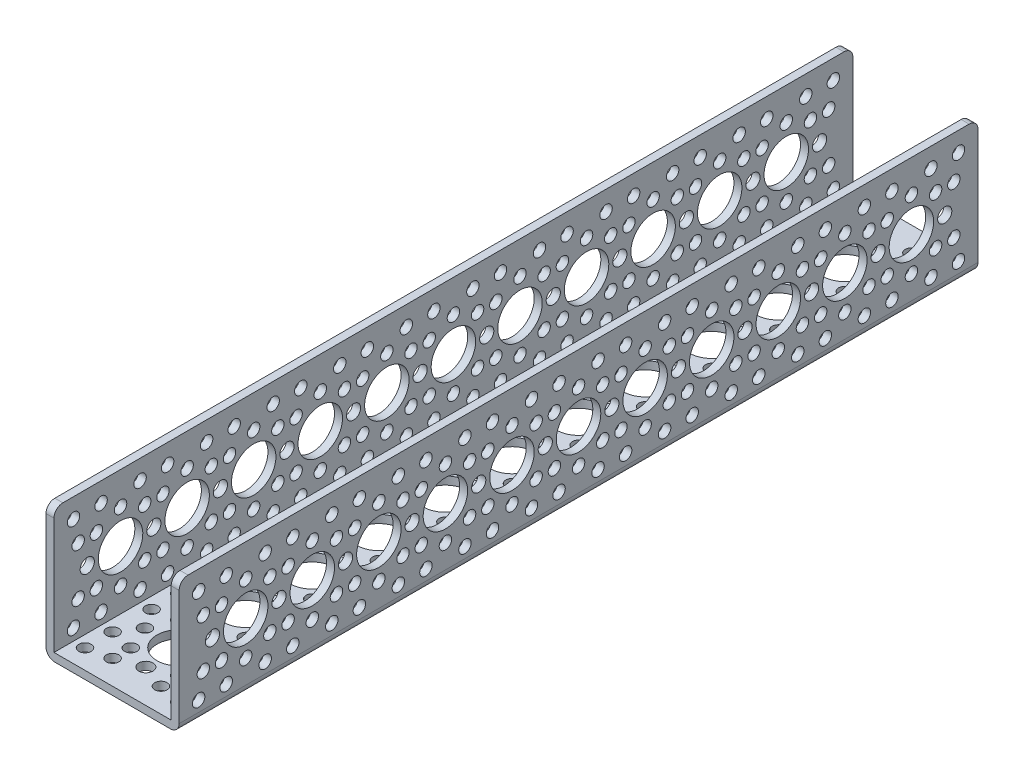
SolidWorks part; units mm, degrees
ref_plane "Front Plane" through (0, 0, 0) normal (0, 0, 1) x (1, 0, 0)
ref_plane "Top Plane" through (0, 0, 0) normal (0, 1, 0) x (1, 0, 0)
ref_plane "Right Plane" through (0, 0, 0) normal (1, 0, 0) x (0, 0, -1)
ref_plane "Plane1" through (38.1, 0, 0) normal (1, 0, 0) x (0, 0, -1)
sketch "Sketch1" plane through (38.1, 0, 0) normal (1, 0, 0) x (0, 0, -1)
  line L0 (0, 38.1) -> (-228.6, 38.1)
  line L1 (-228.6, 38.1) -> (-228.6, 0)
  line L2 (-228.6, 0) -> (0, 0)
  line L3 (0, 0) -> (0, 38.1)
extrude "Boss-Extrude1" add sketch "Sketch1" against normal blind 38.1
sketch "Sketch2" plane through (0, 0, 228.6) normal (0, 0, 1) x (1, 0, 0)
  line L0 (35.814, 38.1) -> (2.286, 38.1)
  line L1 (2.286, 38.1) -> (2.286, 2.286)
  line L2 (2.286, 2.286) -> (35.814, 2.286)
  line L3 (35.814, 2.286) -> (35.814, 38.1)
extrude "Cut-Extrude1" cut sketch "Sketch2" against normal through all
hole_wizard "Hole1" positions "Sketch4" profile "Sketch3" legacy
sketch "Sketch4" plane through (0, 0, 0) normal (-1, 0, 0) x (0, 0, 1)
  point P0 (38.1, 19.05)
  point P1 (19.05, 19.05)
  point P2 (57.15, 19.05)
  point P3 (76.2, 19.05)
  point P4 (95.25, 19.05)
  point P5 (114.3, 19.05)
  point P6 (133.35, 19.05)
  point P7 (152.4, 19.05)
  point P8 (171.45, 19.05)
  point P9 (190.5, 19.05)
  point P10 (209.55, 19.05)
sketch "Sketch3" plane through (0, 19.05, 38.1) normal (0, 1, 0) x (0, 0, 1)
  line L0 (0, 0) -> (0, 2.286)
  line L1 (0, 2.286) -> (6.3627, 2.286)
  line L2 (6.3627, 2.286) -> (6.3627, 0)
  line L3 (6.3627, 0) -> (0, 0)
  line L4 (0, 110) -> (0, -10) construction
  dimension "Diameter" = 12.7254
  dimension "Depth" = 2.286
hole_wizard "#5 Clearance Hole1" positions "Sketch6" profile "Sketch5" hole size "#5" standard "ANSI Inch"
sketch "Sketch6" plane through (0, 0, 0) normal (-1, 0, 0) x (0, 0, 1)
  point P0 (215.1296, 5.5796)
  point P1 (221.6852, 12.1352)
  point P2 (215.1296, 32.5204)
  point P3 (221.6852, 25.9648)
  point P4 (13.4704, 5.5796)
  point P5 (6.9148, 12.1352)
  point P6 (13.4704, 32.5204)
  point P7 (6.9148, 25.9648)
  point P8 (196.0796, 5.5796)
  point P9 (177.0296, 5.5796)
  point P10 (157.9796, 5.5796)
  point P11 (138.9296, 5.5796)
  point P12 (119.8796, 5.5796)
  point P13 (100.8296, 5.5796)
  point P14 (81.7796, 5.5796)
  point P15 (62.7296, 5.5796)
  point P16 (43.6796, 5.5796)
  point P17 (24.6296, 5.5796)
  point P18 (196.0796, 32.5204)
  point P19 (177.0296, 32.5204)
  point P20 (157.9796, 32.5204)
  point P21 (138.9296, 32.5204)
  point P22 (119.8796, 32.5204)
  point P23 (100.8296, 32.5204)
  point P24 (81.7796, 32.5204)
  point P25 (62.7296, 32.5204)
  point P26 (43.6796, 32.5204)
  point P27 (24.6296, 32.5204)
  point P28 (223.0204, 5.5796)
  point P29 (223.0204, 32.5204)
  point P30 (203.9704, 5.5796)
  point P31 (203.9704, 32.5204)
  point P32 (184.9204, 5.5796)
  point P33 (184.9204, 32.5204)
  point P34 (165.8704, 5.5796)
  point P35 (165.8704, 32.5204)
  point P36 (146.8204, 5.5796)
  point P37 (146.8204, 32.5204)
  point P38 (127.7704, 5.5796)
  point P39 (127.7704, 32.5204)
  point P40 (108.7204, 5.5796)
  point P41 (108.7204, 32.5204)
  point P42 (89.6704, 5.5796)
  point P43 (89.6704, 32.5204)
  point P44 (70.6204, 5.5796)
  point P45 (70.6204, 32.5204)
  point P46 (51.5704, 5.5796)
  point P47 (51.5704, 32.5204)
  point P48 (202.6352, 12.1352)
  point P49 (209.55, 9.271)
  point P50 (216.4648, 12.1352)
  point P51 (216.4648, 25.9648)
  point P52 (209.55, 28.829)
  point P53 (183.5852, 12.1352)
  point P54 (190.5, 9.271)
  point P55 (197.4148, 12.1352)
  point P56 (197.4148, 25.9648)
  point P57 (190.5, 28.829)
  point P58 (164.5352, 12.1352)
  point P59 (171.45, 9.271)
  point P60 (178.3648, 12.1352)
  point P61 (178.3648, 25.9648)
  point P62 (171.45, 28.829)
  point P63 (145.4852, 12.1352)
  point P64 (152.4, 9.271)
  point P65 (159.3148, 12.1352)
  point P66 (159.3148, 25.9648)
  point P67 (152.4, 28.829)
  point P68 (126.4352, 12.1352)
  point P69 (133.35, 9.271)
  point P70 (140.2648, 12.1352)
  point P71 (140.2648, 25.9648)
  point P72 (133.35, 28.829)
  point P73 (107.3852, 12.1352)
  point P74 (114.3, 9.271)
  point P75 (121.2148, 12.1352)
  point P76 (121.2148, 25.9648)
  point P77 (114.3, 28.829)
  point P78 (88.3352, 12.1352)
  point P79 (95.25, 9.271)
  point P80 (102.1648, 12.1352)
  point P81 (102.1648, 25.9648)
  point P82 (95.25, 28.829)
  point P83 (69.2852, 12.1352)
  point P84 (76.2, 9.271)
  point P85 (83.1148, 12.1352)
  point P86 (83.1148, 25.9648)
  point P87 (76.2, 28.829)
  point P88 (50.2352, 12.1352)
  point P89 (57.15, 9.271)
  point P90 (64.0648, 12.1352)
  point P91 (64.0648, 25.9648)
  point P92 (57.15, 28.829)
  point P93 (31.1852, 12.1352)
  point P94 (38.1, 9.271)
  point P95 (45.0148, 12.1352)
  point P96 (45.0148, 25.9648)
  point P97 (38.1, 28.829)
  point P98 (202.6352, 25.9648)
  point P99 (183.5852, 25.9648)
  point P100 (164.5352, 25.9648)
  point P101 (145.4852, 25.9648)
  point P102 (126.4352, 25.9648)
  point P103 (107.3852, 25.9648)
  point P104 (88.3352, 25.9648)
  point P105 (69.2852, 25.9648)
  point P106 (50.2352, 25.9648)
  point P107 (31.1852, 25.9648)
  point P108 (32.5204, 5.5796)
  point P109 (32.5204, 32.5204)
  point P110 (5.5796, 5.5796)
  point P111 (5.5796, 32.5204)
  point P112 (12.1352, 12.1352)
  point P113 (19.05, 9.271)
  point P114 (25.9648, 12.1352)
  point P115 (25.9648, 25.9648)
  point P116 (19.05, 28.829)
  point P117 (12.1352, 25.9648)
sketch "Sketch5" plane through (0, 5.5796, 215.1296) normal (0, 1, 0) x (0, 0, 1)
  line L0 (0, 0) -> (0, 2.286)
  line L1 (0, 2.286) -> (1.778, 2.286)
  line L2 (1.778, 2.286) -> (1.778, 0)
  line L5 (1.778, 0) -> (0, 0)
  line L11 (0, -6.35) -> (0, 107.95) construction
  dimension "Thru Hole Dia." = 3.556
  dimension "Thru Hole Depth" = 2.286
hole_wizard "#6 Clearance Hole1" positions "Sketch8" profile "Sketch7" hole size "#6" standard "ANSI Inch"
sketch "Sketch8" plane through (0, 0, 0) normal (-1, 0, 0) x (0, 0, 1)
  point P0 (219.075, 19.05)
  point P1 (200.025, 19.05)
  point P2 (180.975, 19.05)
  point P3 (161.925, 19.05)
  point P4 (142.875, 19.05)
  point P5 (123.825, 19.05)
  point P6 (104.775, 19.05)
  point P7 (85.725, 19.05)
  point P8 (66.675, 19.05)
  point P9 (47.625, 19.05)
  point P10 (28.575, 19.05)
  point P11 (9.525, 19.05)
sketch "Sketch7" plane through (0, 19.05, 219.075) normal (0, 1, 0) x (0, 0, 1)
  line L0 (0, 0) -> (0, 2.286)
  line L1 (0, 2.286) -> (2.032, 2.286)
  line L2 (2.032, 2.286) -> (2.032, 0)
  line L5 (2.032, 0) -> (0, 0)
  line L11 (0, -6.35) -> (0, 107.95) construction
  dimension "Thru Hole Dia." = 4.064
  dimension "Thru Hole Depth" = 2.286
hole_wizard "Hole2" positions "Sketch10" profile "Sketch9" legacy
sketch "Sketch10" plane through (0, 0, 0) normal (0, -1, 0) x (-1, 0, 0)
  point P0 (-19.05, -209.55)
  point P1 (-19.05, -190.5)
  point P2 (-19.05, -171.45)
  point P3 (-19.05, -152.4)
  point P4 (-19.05, -133.35)
  point P5 (-19.05, -114.3)
  point P6 (-19.05, -95.25)
  point P7 (-19.05, -76.2)
  point P8 (-19.05, -57.15)
  point P9 (-19.05, -38.1)
  point P10 (-19.05, -19.05)
sketch "Sketch9" plane through (19.05, 0, 209.55) normal (1, 0, 0) x (0, 0, -1)
  line L0 (0, 0) -> (0, 38.1)
  line L1 (0, 38.1) -> (6.3627, 38.1)
  line L2 (6.3627, 38.1) -> (6.3627, 0)
  line L3 (6.3627, 0) -> (0, 0)
  line L4 (0, 110) -> (0, -10) construction
  dimension "Diameter" = 12.7254
  dimension "Depth" = 38.1
hole_wizard "#6 Clearance Hole2" positions "Sketch12" profile "Sketch11" hole size "#6" standard "ANSI Inch"
sketch "Sketch12" plane through (0, 0, 0) normal (0, -1, 0) x (-1, 0, 0)
  point P0 (-19.05, -219.075)
  point P1 (-19.05, -200.025)
  point P2 (-19.05, -180.975)
  point P3 (-19.05, -161.925)
  point P4 (-19.05, -142.875)
  point P5 (-19.05, -123.825)
  point P6 (-19.05, -104.775)
  point P7 (-19.05, -85.725)
  point P8 (-19.05, -66.675)
  point P9 (-19.05, -47.625)
  point P10 (-19.05, -28.575)
  point P11 (-19.05, -9.525)
sketch "Sketch11" plane through (19.05, 0, 219.075) normal (1, 0, 0) x (0, 0, -1)
  line L0 (0, 0) -> (0, 38.1)
  line L1 (0, 38.1) -> (2.032, 38.1)
  line L2 (2.032, 38.1) -> (2.032, 0)
  line L5 (2.032, 0) -> (0, 0)
  line L11 (0, -6.35) -> (0, 107.95) construction
  dimension "Thru Hole Dia." = 4.064
  dimension "Thru Hole Depth" = 38.1
hole_wizard "#5 Clearance Hole2" positions "Sketch14" profile "Sketch13" hole size "#5" standard "ANSI Inch"
sketch "Sketch14" plane through (0, 0, 0) normal (0, -1, 0) x (-1, 0, 0)
  point P0 (-5.5796, -223.0204)
  point P1 (-5.5796, -215.1296)
  point P2 (-12.1352, -221.6852)
  point P3 (-32.5204, -223.0204)
  point P4 (-32.5204, -215.1296)
  point P5 (-25.9648, -221.6852)
  point P6 (-5.5796, -203.9704)
  point P7 (-5.5796, -196.0796)
  point P8 (-32.5204, -203.9704)
  point P9 (-32.5204, -196.0796)
  point P10 (-5.5796, -184.9204)
  point P11 (-5.5796, -177.0296)
  point P12 (-32.5204, -184.9204)
  point P13 (-32.5204, -177.0296)
  point P14 (-5.5796, -165.8704)
  point P15 (-5.5796, -157.9796)
  point P16 (-32.5204, -165.8704)
  point P17 (-32.5204, -157.9796)
  point P18 (-5.5796, -146.8204)
  point P19 (-5.5796, -138.9296)
  point P20 (-32.5204, -146.8204)
  point P21 (-32.5204, -138.9296)
  point P22 (-5.5796, -127.7704)
  point P23 (-5.5796, -119.8796)
  point P24 (-32.5204, -127.7704)
  point P25 (-32.5204, -119.8796)
  point P26 (-5.5796, -108.7204)
  point P27 (-5.5796, -100.8296)
  point P28 (-32.5204, -108.7204)
  point P29 (-32.5204, -100.8296)
  point P30 (-5.5796, -89.6704)
  point P31 (-5.5796, -81.7796)
  point P32 (-32.5204, -89.6704)
  point P33 (-32.5204, -81.7796)
  point P34 (-5.5796, -70.6204)
  point P35 (-5.5796, -62.7296)
  point P36 (-32.5204, -70.6204)
  point P37 (-32.5204, -62.7296)
  point P38 (-5.5796, -51.5704)
  point P39 (-5.5796, -43.6796)
  point P40 (-32.5204, -51.5704)
  point P41 (-32.5204, -43.6796)
  point P42 (-12.1352, -202.6352)
  point P43 (-9.271, -209.55)
  point P44 (-12.1352, -216.4648)
  point P45 (-25.9648, -216.4648)
  point P46 (-28.829, -209.55)
  point P47 (-25.9648, -202.6352)
  point P48 (-12.1352, -183.5852)
  point P49 (-9.271, -190.5)
  point P50 (-12.1352, -197.4148)
  point P51 (-25.9648, -197.4148)
  point P52 (-28.829, -190.5)
  point P53 (-25.9648, -183.5852)
  point P54 (-12.1352, -164.5352)
  point P55 (-9.271, -171.45)
  point P56 (-12.1352, -178.3648)
  point P57 (-25.9648, -178.3648)
  point P58 (-28.829, -171.45)
  point P59 (-25.9648, -164.5352)
  point P60 (-12.1352, -145.4852)
  point P61 (-9.271, -152.4)
  point P62 (-12.1352, -159.3148)
  point P63 (-25.9648, -159.3148)
  point P64 (-28.829, -152.4)
  point P65 (-25.9648, -145.4852)
  point P66 (-12.1352, -126.4352)
  point P67 (-9.271, -133.35)
  point P68 (-12.1352, -140.2648)
  point P69 (-25.9648, -140.2648)
  point P70 (-28.829, -133.35)
  point P71 (-25.9648, -126.4352)
  point P72 (-12.1352, -107.3852)
  point P73 (-9.271, -114.3)
  point P74 (-12.1352, -121.2148)
  point P75 (-25.9648, -121.2148)
  point P76 (-28.829, -114.3)
  point P77 (-25.9648, -107.3852)
  point P78 (-12.1352, -88.3352)
  point P79 (-9.271, -95.25)
  point P80 (-12.1352, -102.1648)
  point P81 (-25.9648, -102.1648)
  point P82 (-28.829, -95.25)
  point P83 (-25.9648, -88.3352)
  point P84 (-12.1352, -69.2852)
  point P85 (-9.271, -76.2)
  point P86 (-12.1352, -83.1148)
  point P87 (-25.9648, -83.1148)
  point P88 (-28.829, -76.2)
  point P89 (-25.9648, -69.2852)
  point P90 (-12.1352, -50.2352)
  point P91 (-9.271, -57.15)
  point P92 (-12.1352, -64.0648)
  point P93 (-25.9648, -64.0648)
  point P94 (-28.829, -57.15)
  point P95 (-25.9648, -50.2352)
  point P96 (-9.271, -38.1)
  point P97 (-12.1352, -45.0148)
  point P98 (-25.9648, -45.0148)
  point P99 (-28.829, -38.1)
  point P100 (-5.5796, -32.5204)
  point P101 (-5.5796, -24.6296)
  point P102 (-12.1352, -31.1852)
  point P103 (-32.5204, -32.5204)
  point P104 (-32.5204, -24.6296)
  point P105 (-25.9648, -31.1852)
  point P106 (-5.5796, -5.5796)
  point P107 (-5.5796, -13.4704)
  point P108 (-12.1352, -6.9148)
  point P109 (-32.5204, -5.5796)
  point P110 (-32.5204, -13.4704)
  point P111 (-25.9648, -6.9148)
  point P112 (-12.1352, -12.1352)
  point P113 (-9.271, -19.05)
  point P114 (-12.1352, -25.9648)
  point P115 (-25.9648, -25.9648)
  point P116 (-28.829, -19.05)
  point P117 (-25.9648, -12.1352)
sketch "Sketch13" plane through (5.5796, 0, 223.0204) normal (1, 0, 0) x (0, 0, -1)
  line L0 (0, 0) -> (0, 38.1)
  line L1 (0, 38.1) -> (1.778, 38.1)
  line L2 (1.778, 38.1) -> (1.778, 0)
  line L5 (1.778, 0) -> (0, 0)
  line L11 (0, -6.35) -> (0, 107.95) construction
  dimension "Thru Hole Dia." = 3.556
  dimension "Thru Hole Depth" = 38.1
hole_wizard "Hole3" positions "Sketch16" profile "Sketch15" legacy
sketch "Sketch16" plane through (38.1, 0, 0) normal (1, 0, 0) x (0, 0, -1)
  point P0 (-38.1, 19.05)
  point P1 (-19.05, 19.05)
  point P2 (-57.15, 19.05)
  point P3 (-76.2, 19.05)
  point P4 (-95.25, 19.05)
  point P5 (-114.3, 19.05)
  point P6 (-133.35, 19.05)
  point P7 (-152.4, 19.05)
  point P8 (-171.45, 19.05)
  point P9 (-190.5, 19.05)
  point P10 (-209.55, 19.05)
sketch "Sketch15" plane through (38.1, 19.05, 38.1) normal (0, 1, 0) x (0, 0, -1)
  line L0 (0, 0) -> (0, 38.1)
  line L1 (0, 38.1) -> (6.3627, 38.1)
  line L2 (6.3627, 38.1) -> (6.3627, 0)
  line L3 (6.3627, 0) -> (0, 0)
  line L4 (0, 110) -> (0, -10) construction
  dimension "Diameter" = 12.7254
  dimension "Depth" = 38.1
hole_wizard "#6 Clearance Hole3" positions "Sketch18" profile "Sketch17" hole size "#6" standard "ANSI Inch"
sketch "Sketch18" plane through (38.1, 0, 0) normal (1, 0, 0) x (0, 0, -1)
  point P0 (-200.025, 19.05)
  point P1 (-161.925, 19.05)
  point P2 (-123.825, 19.05)
  point P3 (-85.725, 19.05)
  point P4 (-47.625, 19.05)
  point P5 (-9.525, 19.05)
  point P6 (-28.575, 19.05)
  point P7 (-66.675, 19.05)
  point P8 (-104.775, 19.05)
  point P9 (-142.875, 19.05)
  point P10 (-180.975, 19.05)
  point P11 (-219.075, 19.05)
sketch "Sketch17" plane through (38.1, 19.05, 200.025) normal (0, 1, 0) x (0, 0, -1)
  line L0 (0, 0) -> (0, 38.1)
  line L1 (0, 38.1) -> (2.032, 38.1)
  line L2 (2.032, 38.1) -> (2.032, 0)
  line L5 (2.032, 0) -> (0, 0)
  line L11 (0, -6.35) -> (0, 107.95) construction
  dimension "Thru Hole Dia." = 4.064
  dimension "Thru Hole Depth" = 38.1
hole_wizard "#5 Clearance Hole3" positions "Sketch20" profile "Sketch19" hole size "#5" standard "ANSI Inch"
sketch "Sketch20" plane through (38.1, 0, 0) normal (1, 0, 0) x (0, 0, -1)
  point P0 (-215.1296, 5.5796)
  point P1 (-215.1296, 32.5204)
  point P2 (-13.4704, 5.5796)
  point P3 (-196.0796, 5.5796)
  point P4 (-157.9796, 5.5796)
  point P5 (-119.8796, 5.5796)
  point P6 (-81.7796, 5.5796)
  point P7 (-43.6796, 5.5796)
  point P8 (-196.0796, 32.5204)
  point P9 (-157.9796, 32.5204)
  point P10 (-119.8796, 32.5204)
  point P11 (-81.7796, 32.5204)
  point P12 (-43.6796, 32.5204)
  point P13 (-223.0204, 5.5796)
  point P14 (-203.9704, 5.5796)
  point P15 (-184.9204, 5.5796)
  point P16 (-165.8704, 5.5796)
  point P17 (-146.8204, 5.5796)
  point P18 (-127.7704, 5.5796)
  point P19 (-108.7204, 5.5796)
  point P20 (-89.6704, 5.5796)
  point P21 (-70.6204, 5.5796)
  point P22 (-51.5704, 5.5796)
  point P23 (-209.55, 9.271)
  point P24 (-216.4648, 25.9648)
  point P25 (-183.5852, 12.1352)
  point P26 (-197.4148, 12.1352)
  point P27 (-190.5, 28.829)
  point P28 (-171.45, 9.271)
  point P29 (-178.3648, 25.9648)
  point P30 (-145.4852, 12.1352)
  point P31 (-159.3148, 12.1352)
  point P32 (-152.4, 28.829)
  point P33 (-133.35, 9.271)
  point P34 (-140.2648, 25.9648)
  point P35 (-107.3852, 12.1352)
  point P36 (-121.2148, 12.1352)
  point P37 (-114.3, 28.829)
  point P38 (-95.25, 9.271)
  point P39 (-102.1648, 25.9648)
  point P40 (-69.2852, 12.1352)
  point P41 (-83.1148, 12.1352)
  point P42 (-76.2, 28.829)
  point P43 (-57.15, 9.271)
  point P44 (-64.0648, 25.9648)
  point P45 (-31.1852, 12.1352)
  point P46 (-45.0148, 12.1352)
  point P47 (-38.1, 28.829)
  point P48 (-183.5852, 25.9648)
  point P49 (-145.4852, 25.9648)
  point P50 (-107.3852, 25.9648)
  point P51 (-69.2852, 25.9648)
  point P52 (-31.1852, 25.9648)
  point P53 (-12.1352, 12.1352)
  point P54 (-19.05, 9.271)
  point P55 (-25.9648, 12.1352)
  point P56 (-25.9648, 25.9648)
  point P57 (-19.05, 28.829)
  point P58 (-12.1352, 25.9648)
  point P59 (-5.5796, 32.5204)
  point P60 (-5.5796, 5.5796)
  point P61 (-32.5204, 32.5204)
  point P62 (-32.5204, 5.5796)
  point P63 (-50.2352, 25.9648)
  point P64 (-88.3352, 25.9648)
  point P65 (-126.4352, 25.9648)
  point P66 (-164.5352, 25.9648)
  point P67 (-202.6352, 25.9648)
  point P68 (-45.0148, 25.9648)
  point P69 (-38.1, 9.271)
  point P70 (-57.15, 28.829)
  point P71 (-64.0648, 12.1352)
  point P72 (-50.2352, 12.1352)
  point P73 (-83.1148, 25.9648)
  point P74 (-76.2, 9.271)
  point P75 (-95.25, 28.829)
  point P76 (-102.1648, 12.1352)
  point P77 (-88.3352, 12.1352)
  point P78 (-121.2148, 25.9648)
  point P79 (-114.3, 9.271)
  point P80 (-133.35, 28.829)
  point P81 (-140.2648, 12.1352)
  point P82 (-126.4352, 12.1352)
  point P83 (-159.3148, 25.9648)
  point P84 (-152.4, 9.271)
  point P85 (-171.45, 28.829)
  point P86 (-178.3648, 12.1352)
  point P87 (-164.5352, 12.1352)
  point P88 (-197.4148, 25.9648)
  point P89 (-190.5, 9.271)
  point P90 (-209.55, 28.829)
  point P91 (-216.4648, 12.1352)
  point P92 (-202.6352, 12.1352)
  point P93 (-51.5704, 32.5204)
  point P94 (-70.6204, 32.5204)
  point P95 (-89.6704, 32.5204)
  point P96 (-108.7204, 32.5204)
  point P97 (-127.7704, 32.5204)
  point P98 (-146.8204, 32.5204)
  point P99 (-165.8704, 32.5204)
  point P100 (-184.9204, 32.5204)
  point P101 (-203.9704, 32.5204)
  point P102 (-223.0204, 32.5204)
  point P103 (-24.6296, 32.5204)
  point P104 (-62.7296, 32.5204)
  point P105 (-100.8296, 32.5204)
  point P106 (-138.9296, 32.5204)
  point P107 (-177.0296, 32.5204)
  point P108 (-24.6296, 5.5796)
  point P109 (-62.7296, 5.5796)
  point P110 (-100.8296, 5.5796)
  point P111 (-138.9296, 5.5796)
  point P112 (-177.0296, 5.5796)
  point P113 (-6.9148, 25.9648)
  point P114 (-13.4704, 32.5204)
  point P115 (-6.9148, 12.1352)
  point P116 (-221.6852, 25.9648)
  point P117 (-221.6852, 12.1352)
sketch "Sketch19" plane through (38.1, 5.5796, 215.1296) normal (0, 1, 0) x (0, 0, -1)
  line L0 (0, 0) -> (0, 38.1)
  line L1 (0, 38.1) -> (1.778, 38.1)
  line L2 (1.778, 38.1) -> (1.778, 0)
  line L5 (1.778, 0) -> (0, 0)
  line L11 (0, -6.35) -> (0, 107.95) construction
  dimension "Thru Hole Dia." = 3.556
  dimension "Thru Hole Depth" = 38.1
fillet "Fillet1" radius 2.54 6 edges at (0, 0, 114.3) (1.143, 38.1, 228.6) (1.143, 38.1, 0) (36.957, 38.1, 228.6) (36.957, 38.1, 0) (38.1, 0, 114.3) tangent propagation no
